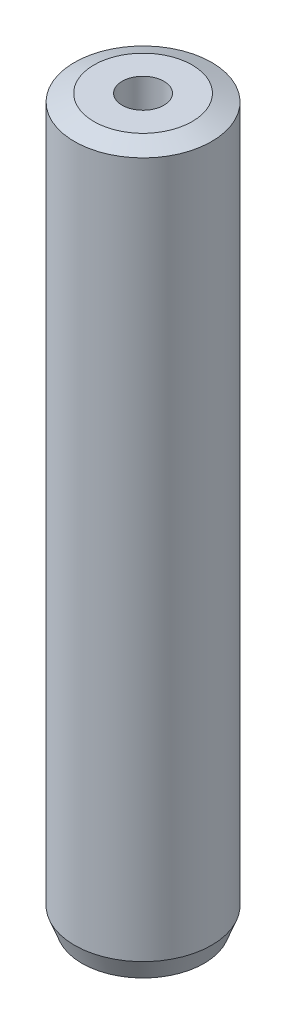
SolidWorks part; units mm, degrees
ref_plane "Front Plane" through (0, 0, 0) normal (0, 0, 1) x (1, 0, 0)
ref_plane "Top Plane" through (0, 0, 0) normal (0, 1, 0) x (1, 0, 0)
ref_plane "Right Plane" through (0, 0, 0) normal (1, 0, 0) x (0, 0, -1)
sketch "Sketch1" plane through (0, 0, 0) normal (0, 1, 0) x (1, 0, 0)
  circle A0 centre (0, 0) radius 42.5
  dimension "SHAFT_OD" = 85
extrude "Boss-Extrude1" add sketch "Sketch1" along normal blind 448.0295
sketch "Sketch2" plane through (0, 0, 0) normal (0, 1, 0) x (1, 0, 0)
  circle A0 centre (0, 0) radius 12.9212
  dimension "BORE_D" = 25.8423
extrude "Cut-Extrude1" cut sketch "Sketch2" along normal through all
chamfer "Chamfer1" distance 4.66 angle 68.917 2 edges at (0, 448.0295, 42.5) (0, 0, 42.5) first distance on face at (0, 448.0295, 42.5) first distance on face at (0, 0, 12.9212)
